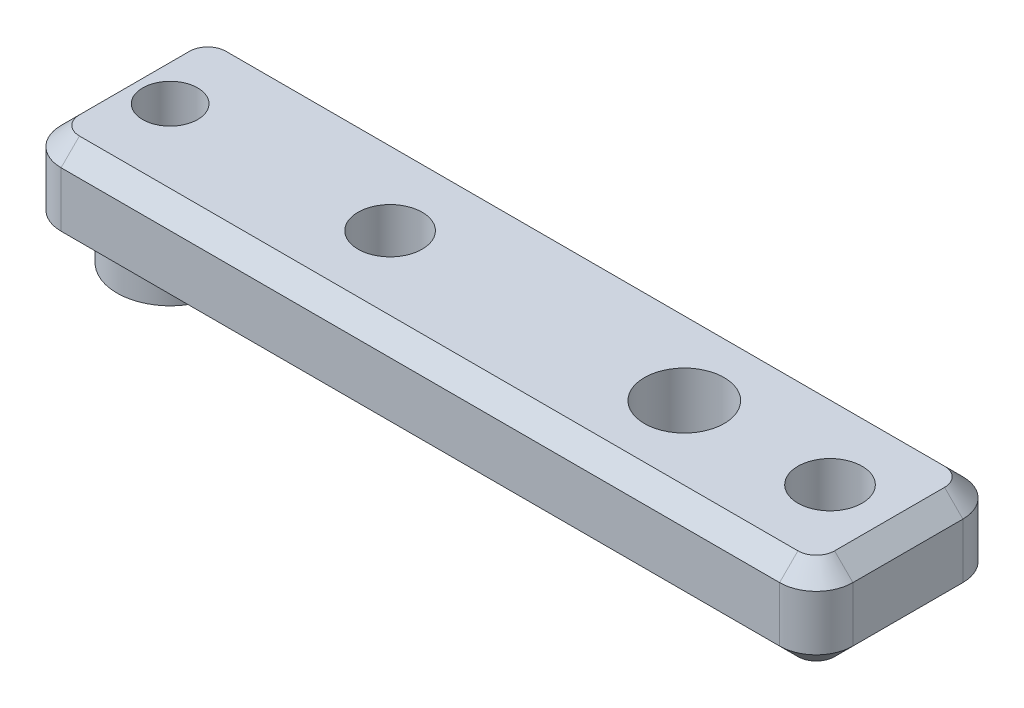
SolidWorks part; units mm, degrees
ref_plane "Front Plane" through (0, 0, 0) normal (0, 0, 1) x (1, 0, 0)
ref_plane "Top Plane" through (0, 0, 0) normal (0, 1, 0) x (1, 0, 0)
ref_plane "Right Plane" through (0, 0, 0) normal (1, 0, 0) x (0, 0, -1)
sketch "Sketch1" plane through (0, 0, 0) normal (0, 1, 0) x (1, 0, 0)
  line L1 (-27, 5) -> (27, 5)
  line L2 (-27, 5) -> (-27, -5)
  line L3 (-27, -5) -> (27, -5)
  line L4 (27, 5) -> (27, -5)
  line L5 (-27, 5) -> (27, -5) construction
  line L6 (-27, -5) -> (27, 5) construction
  point P0 (0, 0)
  dimension "D1" = 54
  dimension "D2" = 10
extrude "Boss-Extrude1" add sketch "Sketch1" along normal blind 5
sketch "Sketch3" plane through (0, 5, 0) normal (0, 1, 0) x (1, 0, 0)
  circle A0 centre (-24.05, 0) radius 1.5
  circle A1 centre (4, 0) radius 2.175
  circle A3 centre (-12.05, 0) radius 1.75
  circle A4 centre (11.95, 0) radius 1.75
  dimension "D3" = 3
  dimension "D4" = 4.35
  dimension "D7" = 3.5
  dimension "D9" = 3.5
  dimension "D1" = 28.05
  dimension "D2" = 4
  dimension "D8" = 12
  dimension "D10" = 24
extrude "Cut-Extrude1" cut sketch "Sketch3" against normal blind 7
fillet "Fillet1" radius 2 4 edges at (27, 2.5, -5) (-27, 2.5, -5) (27, 2.5, 5) (-27, 2.5, 5)
sketch "Sketch4" plane through (0, 0, 0) normal (0, -1, 0) x (1, 0, 0)
  circle A0 centre (-24.05, 0) radius 1.5
  circle A1 centre (-24.05, 0) radius 2.9
  dimension "D1" = 1.4
extrude "Boss-Extrude2" add sketch "Sketch4" along normal blind 2.5
sketch "Sketch5" plane through (0, 5, 0) normal (0, 1, 0) x (1, 0, 0)
  line L0 (25, 5) -> (-25, 5) construction
  line L1 (16.2, 5) -> (30.828, 5)
  line L2 (16.2, 5) -> (16.2, -6.0726)
  line L3 (16.2, -6.0726) -> (30.828, -6.0726)
  line L4 (30.828, 5) -> (30.828, -6.0726)
  circle A2 centre (11.95, 0) radius 1.75 construction
  dimension "D1" = 2.5
extrude "Cut-Extrude2" cut sketch "Sketch5" against normal blind 10
fillet "Fillet2" radius 2 2 edges at (16.2, 2.5, -5) (16.2, 2.5, 5)
chamfer "Chamfer1" distance 1 angle 45 16 edges at (-5.4, 0, -5) (-26.4142, 0, -4.4142) (15.6142, 0, -4.4142) (-27, 0, 0) (16.2, 0, 0) (-26.4142, 0, 4.4142) (15.6142, 0, 4.4142) (-5.4, 0, 5) (-5.4, 5, -5) (-26.4142, 5, -4.4142) (15.6142, 5, -4.4142) (-27, 5, 0) (16.2, 5, 0) (-26.4142, 5, 4.4142) (15.6142, 5, 4.4142) (-5.4, 5, 5)
